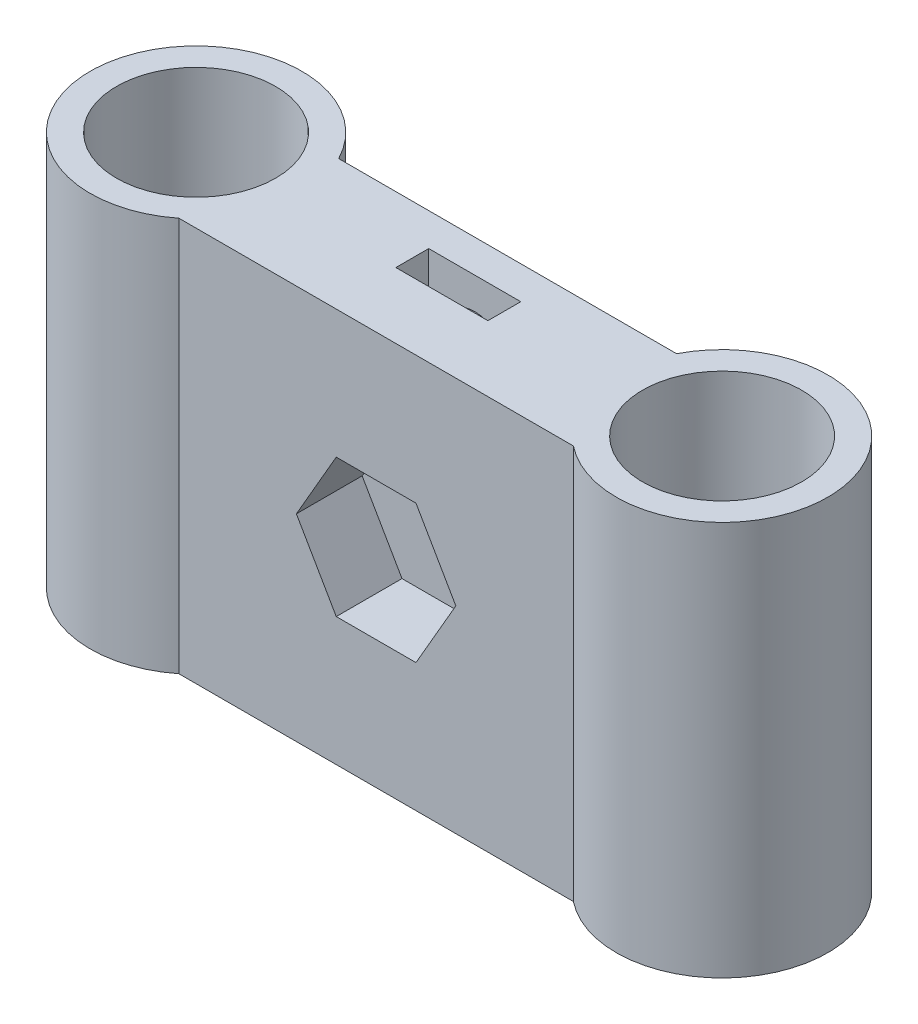
SolidWorks part; units mm, degrees
ref_plane "Přední rovina" through (0, 0, 0) normal (0, 0, 1) x (1, 0, 0)
ref_plane "Horní rovina" through (0, 0, 0) normal (0, 1, 0) x (1, 0, 0)
ref_plane "Pravá rovina" through (0, 0, 0) normal (1, 0, 0) x (0, 0, -1)
sketch "Skica1" plane through (0, 0, 0) normal (0, 0, 1) x (1, 0, 0)
  line L1 (0, 0) -> (-30, 0)
  line L2 (0, 0) -> (0, -30)
  line L3 (0, -30) -> (-30, -30)
  line L4 (-30, 0) -> (-30, -30)
  dimension "D1" = 30
extrude "Přidat vysunutím1" add sketch "Skica1" along normal blind 5 contours L2 L1 L4 L3
sketch "Skica2" plane through (0, 0, 0) normal (0, 0, -1) x (-1, 0, 0)
  line L1 (0, 0) -> (30, 0)
  line L2 (0, 0) -> (0, -30)
  line L3 (0, -30) -> (30, -30)
  line L4 (30, 0) -> (30, -30)
extrude "Přidat vysunutím2" add sketch "Skica2" along normal blind 5
ref_plane "Rovina1" through (0, -30, 0) normal (0, -1, 0) x (-1, 0, 0)
sketch "Skica4" plane through (0, -30, 0) normal (0, -1, 0) x (-1, 0, 0)
  line L0 (0, 5) -> (30, 5) construction
  line L1 (30, -5) -> (30, 5)
  arc A1 (30, -5) -> (30, 5) centre (35.7236, 0) cw
extrude "Odebrat vysunutím1" cut sketch "Skica4" against normal up to surface (30 mm away) contours L1 A1 up to face at (-15, 0, 0)
sketch "Skica5" plane through (0, -30, 0) normal (0, -1, 0) x (-1, 0, 0)
  line L0 (0, -5) -> (0, 5)
  line L1 (0, -5) -> (0, 5) construction
  line L2 (0, -5) -> (0, 5)
  arc A1 (0, -5) -> (0, 5) centre (-5.5902, 0) ccw
  arc A2 (0, -5) -> (0, 5) centre (-5.5902, 0) ccw
  line M5 (0, 5) -> (0, -5)
  dimension "D1" = 7.5
extrude "Odebrat vysunutím2" cut sketch "Skica5" against normal up to surface (30 mm away) contours A1 M5 region at (-0.7729, -30, 0) up to face at (-14.5309, 0, 0)
sketch "Skica7" plane through (0, 0, 0) normal (0, 1, 0) x (1, 0, 0)
  line L0 (0, 0) -> (-30, 0) construction
  line L1 (-18.5, 0) -> (-11.5, 0)
  line L2 (-18.5, 0) -> (-18.5, 2.5)
  line L3 (-18.5, 2.5) -> (-11.5, 2.5)
  line L4 (-11.5, 0) -> (-11.5, 2.5)
  line L5 (-15, 5) -> (-15, 0) construction
  line L6 (-30, 5) -> (0, 5) construction
  point P14 (-15, 2.5)
  dimension "D1" = 2.5
  dimension "D3" = 7
extrude "Odebrat vysunutím3" cut sketch "Skica7" against normal up to surface (30 mm away) up to face at (-15.0084, -30, 0)
sketch "Skica10" plane through (0, -30, 0) normal (0, -1, 0) x (1, 0, 0)
  line L0 (-11.5, -1.25) -> (-40.8335, -1.25) construction
  line L1 (-11.5, 0) -> (-11.5, -2.5) construction
  line L2 (-15, 0) -> (-15, -2.5) construction
  line L3 (0, 0) -> (-30, 0) construction
  line L4 (-11.5, -2.5) -> (-18.5, -2.5) construction
  circle A4 centre (-35, -1.3089) radius 6.05
  circle A5 centre (-35, -1.3089) radius 8.05
  circle A6 centre (5, -1.3089) radius 8.05
  circle A7 centre (5, -1.3089) radius 6.05
  dimension "D2" = 12.1
  dimension "D1" = 2
  dimension "D3" = 40
extrude "Přidat vysunutím7" add sketch "Skica10" against normal up to surface (30 mm away) up to face at (-15, 0, -1.25)
sketch "Skica11" plane through (0, -30, 0) normal (0, -1, 0) x (-1, 0, 0)
  line L0 (15, 5) -> (15, -5) construction
  line L1 (2.1539, 5) -> (27.8461, 5) construction
  line L2 (0, -5) -> (30, -5) construction
sketch "Skica13" plane through (0, 0, -5) normal (0, 0, -1) x (-1, 0, 0)
  line L0 (15, -30) -> (15, 0) construction
  line L1 (18.5, -20.5) -> (11.5, -20.5)
  line L2 (18.5, -20.5) -> (18.5, -17.5)
  line L3 (18.5, -17.5) -> (11.5, -17.5)
  line L4 (11.5, -20.5) -> (11.5, -17.5)
  line L5 (18.5, -12.5) -> (11.5, -12.5)
  line L6 (18.5, -12.5) -> (18.5, -9.5)
  line L7 (18.5, -9.5) -> (11.5, -9.5)
  line L8 (11.5, -12.5) -> (11.5, -9.5)
  line L9 (15, -15) -> (7.9569, -15) construction
  point P12 (15, -20.5)
  point P13 (15, -12.5)
  dimension "D1" = 7
  dimension "D2" = 5
  dimension "D3" = 3
extrude "Odebrat vysunutím5" cut sketch "Skica13" against normal up to surface (2.5 mm away) up to face at (-15, -15, -2.5)
sketch "Skica15" plane through (0, 0, -2.5) normal (0, 0, 1) x (1, 0, 0)
  line L0 (-15, -9.5) -> (-15, 0) construction
  line L1 (-11.5, -9.5) -> (-18.5, -9.5) construction
  line L2 (-15, -20.5) -> (-15, -30) construction
  line L3 (-18.5, -20.5) -> (-11.5, -20.5) construction
  line L4 (-11.5, -30) -> (-18.5, -30) construction
  line L5 (-15, -20.5) -> (-15, -9.5) construction
  line L6 (-15, -15) -> (-25.4934, -15) construction
  circle A0 centre (-15, -25.25) radius 2.35
  circle A1 centre (-15, -4.75) radius 2.35
  point P14 (-15, -25.25)
  dimension "D1" = 4.7
extrude "Odebrat vysunutím6" cut sketch "Skica15" against normal blind 1.7
sketch "Skica16" plane through (0, 0, -5) normal (0, 0, -1) x (-1, 0, 0)
  line L0 (15, 0) -> (15, -30) construction
  line L1 (27.8461, 0) -> (2.1539, 0) construction
  line L2 (2.1539, -30) -> (27.8461, -30) construction
  line L3 (15, 0) -> (15, -9.5)
  line L4 (18.5, -12.5) -> (11.5, -12.5)
  line L5 (18.5, -12.5) -> (18.5, -17.5)
  line L6 (18.5, -17.5) -> (11.5, -17.5)
  line L7 (11.5, -12.5) -> (11.5, -17.5)
  line L8 (18.5, -9.5) -> (11.5, -9.5) construction
  line L9 (15, -30) -> (15, -20.5)
  line L10 (11.5, -20.5) -> (18.5, -20.5) construction
  circle A0 centre (15, -4.75) radius 1
  circle A1 centre (15, -25.25) radius 1
  point P22 (15, -4.75)
  point P23 (15, -25.25)
  point P24 (0, 0)
  point P25 (18.25, -12.5)
  point P27 (11.75, -17.5)
  line M11 (11.5, -17.5) -> (18.5, -17.5)
  line M13 (18.5, -12.5) -> (11.5, -12.5)
  dimension "D1" = 2
  dimension "D2" = 2
extrude "Přidat vysunutím8" add sketch "Skica16" against normal up to surface (5 mm away) contours L0 L4 L7 M11 | L0 L6 L5 M13 region at (-16.75, -15, -5) region at (-13.25, -15, -5) up to face at (-15, -15, 0)
extrude "Odebrat vysunutím7" cut sketch "Skica16<3>" against normal up to surface (0.8 mm away) contours L3 A0 | L3 A0 | L9 A1 | L9 A1 region at (-15.4244, -4.75, -5) region at (-14.5756, -4.75, -5) region at (-14.5756, -25.25, -5) region at (-15.4244, -25.25, -5) up to face at (-17.35, -4.75, -4.2)
sketch "Skica16<3>" plane through (0, 0, -5) normal (0, 0, -1) x (-1, 0, 0) same geometry as "Skica16"
fillet "Zaoblit1" radius 4 2 edges at (-15, -17.5, 0) (-15, -12.5, 0)
fillet "Zaoblit2" radius 4 2 edges at (-15, -20.5, -2.5) (-15, -9.5, -2.5)
sketch "Skica17" plane through (0, 0, 5) normal (0, 0, 1) x (1, 0, 0)
  line L0 (-30, 0) -> (0, -30) construction
  line L1 (0, 0) -> (-30, -30) construction
  line L3 (-8.9378, -15) -> (-11.9689, -9.75)
  line L4 (-30, -30) -> (0, -30)
  line L5 (0, -30) -> (0, 0)
  line L6 (0, 0) -> (-30, 0)
  line L7 (-30, 0) -> (-30, -30)
  line L8 (-30, -30) -> (0, -30) construction
  line L9 (0, -30) -> (0, 0) construction
  line L10 (0, 0) -> (-30, 0) construction
  line L11 (-30, 0) -> (-30, -30) construction
  line L12 (-11.9689, -9.75) -> (-18.0311, -9.75)
  line L13 (-18.0311, -9.75) -> (-21.0622, -15)
  line L14 (-21.0622, -15) -> (-18.0311, -20.25)
  line L15 (-18.0311, -20.25) -> (-11.9689, -20.25)
  line L16 (-11.9689, -20.25) -> (-8.9378, -15)
  circle A0 centre (-15, -15) radius 5.25 construction
  point P4 (0, 0)
  dimension "D2" = 10.5
  dimension "D1" = 0
extrude "Odebrat vysunutím8" cut sketch "Skica17" against normal blind 5
